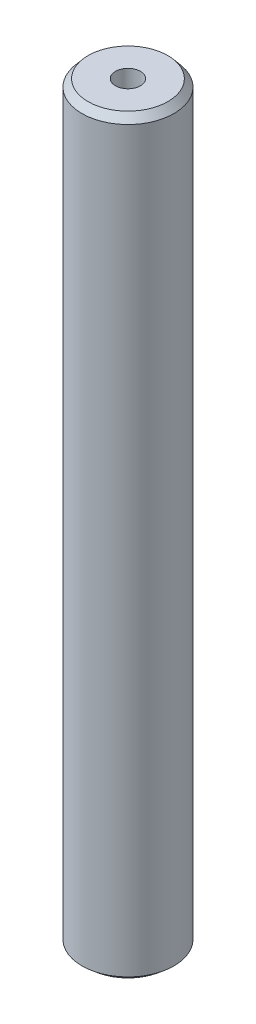
SolidWorks part; units mm, degrees
ref_plane "Front Plane" through (0, 0, 0) normal (0, 0, 1) x (1, 0, 0)
ref_plane "Top Plane" through (0, 0, 0) normal (0, 1, 0) x (1, 0, 0)
ref_plane "Right Plane" through (0, 0, 0) normal (1, 0, 0) x (0, 0, -1)
sketch "Sketch1" plane through (0, 0, 0) normal (0, 1, 0) x (1, 0, 0)
  circle A0 centre (0, 0) radius 17.5
  dimension "SHAFT_OD" = 35
extrude "Boss-Extrude1" add sketch "Sketch1" along normal blind 285.8722
sketch "Sketch2" plane through (0, 0, 0) normal (0, 1, 0) x (1, 0, 0)
  circle A0 centre (0, 0) radius 4.7647
  dimension "BORE_D" = 9.5295
extrude "Cut-Extrude1" cut sketch "Sketch2" along normal through all
chamfer "Chamfer1" distance 2.7776 angle 39.883 2 edges at (0, 285.8722, 17.5) (0, 0, 17.5) first distance on face at (0, 285.8722, 17.5) first distance on face at (0, 0, 4.7647)
